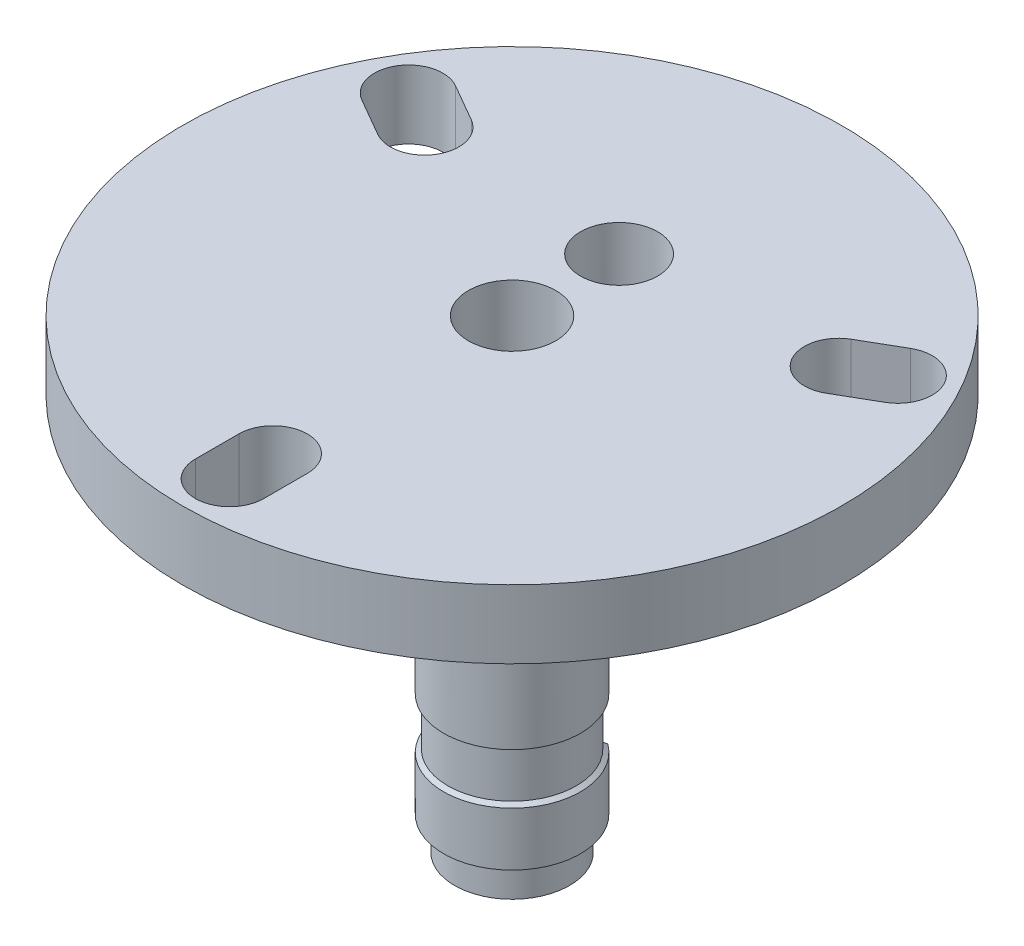
SolidWorks part; units mm, degrees
ref_plane "Front Plane" through (0, 0, 0) normal (0, 0, 1) x (1, 0, 0)
ref_plane "Top Plane" through (0, 0, 0) normal (0, 1, 0) x (1, 0, 0)
ref_plane "Right Plane" through (0, 0, 0) normal (1, 0, 0) x (0, 0, -1)
sketch "Sketch1" plane through (0, 0, 0) normal (0, 1, 0) x (1, 0, 0)
  line L0 (-2, -16.5) -> (-2, -13.96)
  line L1 (2, -16.5) -> (2, -13.96)
  line L2 (0, -16.5) -> (0, 0) construction
  line L3 (0, 0) -> (38.1669, 22.0357) construction
  line L4 (0, 0) -> (-43.0695, 24.8662) construction
  line L5 (-11.0897, 8.7121) -> (-13.0897, 5.2479) construction
  line L6 (-13.2894, 9.9821) -> (-15.2894, 6.5179) construction
  line L7 (11.0897, 8.7121) -> (13.0897, 5.2479) construction
  line L8 (13.2894, 9.9821) -> (15.2894, 6.5179) construction
  line L9 (13.0897, 5.2479) -> (15.2894, 6.5179)
  line L10 (13.2894, 9.9821) -> (11.0897, 8.7121)
  line L11 (-15.2894, 6.5179) -> (-13.0897, 5.2479)
  line L12 (-13.2894, 9.9821) -> (-11.0897, 8.7121)
  circle A0 centre (0, 0) radius 16.5
  circle A1 centre (0, 0) radius 19.25
  arc A2 (-1.9963, -16.3788) -> (1.9963, -16.3788) centre (0, -16.5) ccw
  arc A3 (2, -13.96) -> (-2, -13.96) centre (0, -13.96) ccw
  circle A4 centre (0, 0) radius 4
  arc A5 (15.1826, 6.4605) -> (13.1863, 9.9183) centre (14.2894, 8.25) ccw
  arc A6 (-13.1863, 9.9183) -> (-15.1826, 6.4605) centre (-14.2894, 8.25) ccw
  arc A7 (-13.0897, 5.2479) -> (-11.095, 8.7151) centre (-12.0897, 6.98) ccw
  arc A8 (11.0897, 8.7121) -> (13.0897, 5.2479) centre (12.0897, 6.98) ccw
  dimension "D1" = 38.5
  dimension "D2" = 33
  dimension "D3" = 4
  dimension "D5" = 8
  dimension "D8" = 4
  dimension "D9" = 4
  dimension "D10" = 4
  dimension "D11" = 4
  dimension "D4" = 2.54
  dimension "D6" = 120
  dimension "D7" = 120
  dimension "D12" = 2.54
  dimension "D15" = 2.54
extrude "Boss-Extrude1" add sketch "Sketch1" against normal blind 4 contours A1 A6 L12 A0 L10 A5 L9 L1 A2 L0 L11 | A8 L10 A0 L12 A7 L11 L0 A3 L1 L9 A4 region at (-13.886, 0, 8.0171) region at (-18.7055, 0, 0)
extrude "Boss-Extrude2" add sketch "Sketch1<4>" against normal offset from surface (27.15 mm away) 27.15 contours A4 region at (0, 0, 0) up to face at (-13.1896, 0, -7.615)
sketch "Sketch1<4>" plane through (0, 0, 0) normal (0, 1, 0) x (1, 0, 0) same geometry as "Sketch1"
sketch "Sketch2" plane through (0, 0, 0) normal (1, 0, 0) x (0, 0, -1)
  line L0 (0, 0) -> (0, -27.15) construction
  line L2 (0.8, -27.15) -> (0.8, -25.15)
  line L3 (1, 0) -> (0.8, -25.15)
  line L4 (-4, -27.15) -> (4, -27.15) construction
  line L6 (19.25, 0) -> (-19.25, 0) construction
  line L7 (0, 0) -> (1, 0)
  line L8 (0, -27.15) -> (0.8, -27.15)
  line L9 (0, 0) -> (0, -27.15)
  line L10 (0, -27.15) -> (0.8, -27.15)
  dimension "D1" = 2
  dimension "D2" = 1
  dimension "D3" = 0.8
revolve "Cut-Revolve4" cut sketch "Sketch2" angle 360 about L0 region at (0, -13.0362, -0.4484)
ref_axis "Axis1" through (0, 0, 0) along (0, -1, 0)
sketch "Sketch5" plane through (0, 0, 0) normal (0, 0, 1) x (1, 0, 0)
  line L0 (0, 0) -> (0, -7) construction
  line L1 (0, -7) -> (-2.55, -5.5278)
  line L2 (-2.55, -5.5278) -> (-2.55, 0)
  line L3 (-2.55, 0) -> (0, 0)
  line L4 (1, 0) -> (-1, 0) construction
  line L5 (0, 0) -> (0, -7) construction
  line L6 (0, 0) -> (0, -7)
  dimension "D1" = 7
  dimension "D2" = 60
  dimension "D3" = 2.55
  dimension "D4" = 5.5278
revolve "Cut-Revolve8" cut sketch "Sketch5" angle 360 about axis through (0, 0, 0) along (0, -1, 0)
sketch "Sketch6" plane through (0, -27.15, 0) normal (0, -1, 0) x (1, 0, 0)
  circle A0 centre (0, 0) radius 4
  circle A3 centre (0, 0) radius 4 construction
  circle A4 centre (0, 0) radius 3.356
  circle A5 centre (0, 0) radius 3.356
  dimension "D1" = 0.644
extrude "Cut-Extrude1" cut sketch "Sketch6" against normal blind 1.932
ref_plane "Plane1" through (0, -23, 0) normal (0, 1, 0) x (1, 0, 0)
sketch "Sketch8" plane through (0, -23, 0) normal (0, 1, 0) x (1, 0, 0)
  line L0 (0, 0) -> (0, 6.5) construction
  circle A0 centre (0, 4) radius 2.5
  circle A1 centre (0, 0) radius 4 construction
  dimension "D1" = 5
extrude "Cut-Extrude3" cut sketch "Sketch8" along normal blind 5
chamfer "Chamfer1" distance 2 angle 20 1 edges at (0, -18, -4) first distance on face at (0, -20.5, -3.6094)
sketch "Sketch9" plane through (0, 0, 0) normal (1, 0, 0) x (0, 0, -1)
  line L0 (4, -23) -> (3.2187, -23) construction
  line L1 (-4, -19.125) -> (-3.75, -19.125)
  line L2 (-4, -19.125) -> (-4, -21.875)
  line L3 (-4, -21.875) -> (-3.75, -21.875)
  line L4 (-3.75, -19.125) -> (-3.75, -21.875)
  line L5 (-4, -4) -> (-4, -25.218) construction
  line L6 (0, -27.15) -> (0, 0) construction
  line L7 (-0.8, -27.15) -> (0.8, -27.15) construction
  line L8 (2.55, 0) -> (-2.55, 0) construction
  point P4 (-4, -20.5)
  dimension "D1" = 2.75
  dimension "D2" = 0.25
  dimension "D3" = 2.5
revolve "Cut-Revolve9" cut sketch "Sketch9" angle 360 about L6
chamfer "Chamfer3" distance 0.3 angle 35 1 edges at (0, -21.875, 4) first distance on face at (0, -21.875, 0.3893)
fillet "Fillet3" radius 10 1 edges at (0, -4, 4) second distance 7.5 first distance on face at (0, -4, 4)
sketch "Sketch7" plane through (0, -4, 0) normal (0, -1, 0) x (1, 0, 0)
  line L0 (0, 0) -> (0, -19.25) construction
  circle A0 centre (0, -6.25) radius 2.25
  circle A1 centre (0, 0) radius 4 construction
  circle A2 centre (0, 0) radius 19.25 construction
  dimension "D1" = 4.5
extrude "Cut-Extrude2" cut sketch "Sketch7" against normal through all and the other way through all
